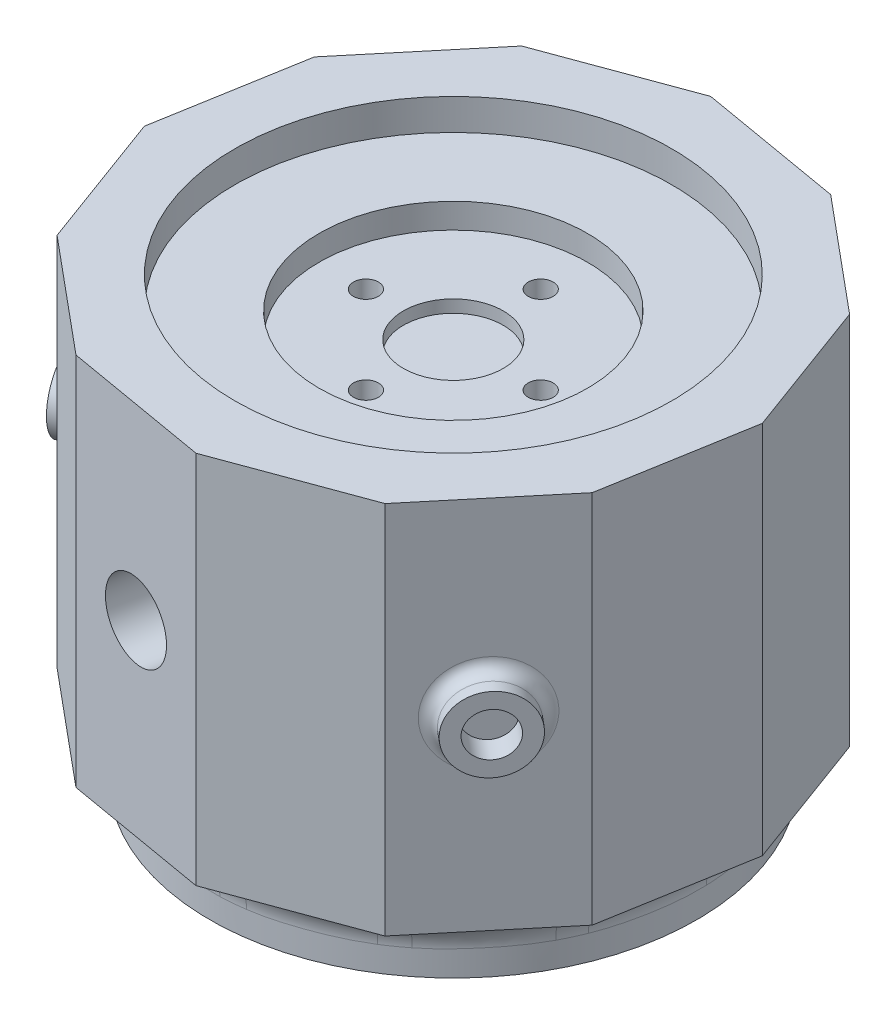
SolidWorks part; units mm, degrees
ref_plane "Front Plane" through (0, 0, 0) normal (0, 0, 1) x (1, 0, 0)
ref_plane "Top Plane" through (0, 0, 0) normal (0, 1, 0) x (1, 0, 0)
ref_plane "Right Plane" through (0, 0, 0) normal (1, 0, 0) x (0, 0, -1)
sketch "Sketch1" plane through (0, 0, 0) normal (0, 1, 0) x (1, 0, 0)
  line L0 (-18.6086, -13.1327) -> (-9.5492, -20.6776)
  line L1 (18.6086, 13.1327) -> (9.5492, 20.6776)
  line L2 (9.5492, 20.6776) -> (-2.0689, 22.6819)
  line L3 (-2.0689, 22.6819) -> (-13.1327, 18.6086)
  line L4 (-13.1327, 18.6086) -> (-20.6776, 9.5492)
  line L5 (-20.6776, 9.5492) -> (-22.6819, -2.0689)
  line L6 (-22.6819, -2.0689) -> (-18.6086, -13.1327)
  line L7 (-9.5492, -20.6776) -> (2.0689, -22.6819)
  line L8 (2.0689, -22.6819) -> (13.1327, -18.6086)
  line L9 (13.1327, -18.6086) -> (20.6776, -9.5492)
  line L10 (20.6776, -9.5492) -> (22.6819, 2.0689)
  line L11 (22.6819, 2.0689) -> (18.6086, 13.1327)
  circle A0 centre (0, 0) radius 22 construction
  circle A1 centre (0, 0) radius 17.5
  dimension "D1" = 35
  dimension "D2" = 44
extrude "Boss-Extrude1" add sketch "Sketch1" along normal blind 30
sketch "Sketch2" plane through (0, 30, 0) normal (0, 1, 0) x (1, 0, 0)
  circle A0 centre (0, 0) radius 17.5
extrude "Boss-Extrude2" add sketch "Sketch2" against normal blind 4.5 from offset 2.5 offset against normal yes
sketch "Sketch3" plane through (0, 23, 0) normal (0, -1, 0) x (1, 0, 0)
  circle A0 centre (0, 0) radius 15.5
  circle A1 centre (0, 0) radius 17.5
  dimension "D1" = 31
  dimension "D2" = 35
extrude "Cut-Extrude1" cut sketch "Sketch3" against normal blind 1.8
sketch "Sketch4" plane through (0, 0, 0) normal (0, -1, 0) x (1, 0, 0)
  circle A0 centre (0, 0) radius 17.5
  circle A1 centre (0, 0) radius 19.5
  dimension "D1" = 35
  dimension "D2" = 39
extrude "Boss-Extrude3" add sketch "Sketch4" along normal blind 5
fillet "Fillet1" radius 3 1 edges at (0, 0, 19.5)
sketch "Sketch5" plane through (3.7401, 0, -21.6797) normal (0.17, 0, -0.9854) x (-0.9854, 0, -0.17)
  line L0 (0, 30) -> (0, 0) construction
  line L1 (-5.8949, 30) -> (5.8949, 30) construction
  circle A0 centre (0, 15) radius 1.75
  circle A1 centre (0, 15) radius 3
  dimension "D2" = 3.5
  dimension "D3" = 6
  dimension "D1" = 15
extrude "Boss-Extrude4" add sketch "Sketch5" along normal blind 2
pattern_circular "CirPattern2" count 3 every 120 about axis through (0, -5, 0) along (0, -1, 0) of "Boss-Extrude4"
fillet "Fillet2" radius 1 3 edges at (6.6965, 15, -21.1697) (-21.6818, 15, 4.7856) (14.9853, 15, 16.3842)
sketch "Sketch6" plane through (0, 27.5, 0) normal (0, 1, 0) x (1, 0, 0)
  line L0 (0, 0) -> (17.5, 0) construction
  circle A0 centre (0, 0) radius 4
  circle A1 centre (0, 0) radius 17.5 construction
  circle A2 centre (7, 0) radius 1
  circle A3 centre (0, 0) radius 10.75
  circle A4 centre (0, -7) radius 1
  circle A5 centre (-7, 0) radius 1
  circle A6 centre (0, 7) radius 1
  point P19 (0, 0)
  dimension "D1" = 8
  dimension "D3" = 2
  dimension "D4" = 21.5
  dimension "D2" = 7
  dimension "D5" = 4
extrude "Cut-Extrude5" cut sketch "Sketch6" against normal blind 2 contours A0 A2 A3 A6 A5 A4 | A0 region at (0, 27.5, 0) region at (-10.4459, 27.5, 0)
extrude "Cut-Extrude6" cut sketch "Sketch6<3>" against normal blind 1 from surface contours A0 region at (0, 27.5, 0) starting at face at (7, 25.5, 1)
sketch "Sketch6<3>" plane through (0, 27.5, 0) normal (0, 1, 0) x (1, 0, 0) same geometry as "Sketch6"
extrude "Cut-Extrude7" cut sketch "Sketch6<4>" against normal through all both and the other way through all contours A5 | A6 | A4 | L0 A2 | A2 L0 region at (7, 27.5, 0.4244) region at (7, 27.5, -0.4244) region at (0, 27.5, 7) region at (-7, 27.5, 0) region at (0, 27.5, -7)
sketch "Sketch6<4>" plane through (0, 27.5, 0) normal (0, 1, 0) x (1, 0, 0) same geometry as "Sketch6"
sketch "Sketch7" plane through (-3.7401, 0, 21.6797) normal (-0.17, 0, 0.9854) x (0.9854, 0, 0.17)
  line L0 (0, 0) -> (0, 30) construction
  line L1 (-5.8949, 30) -> (5.8949, 30) construction
  line L2 (-4.717, 0) -> (4.717, 0) construction
  circle A0 centre (0, 15) radius 3
  dimension "D2" = 6
  dimension "D1" = 15
extrude "Cut-Extrude8" cut sketch "Sketch7" against normal blind 10
